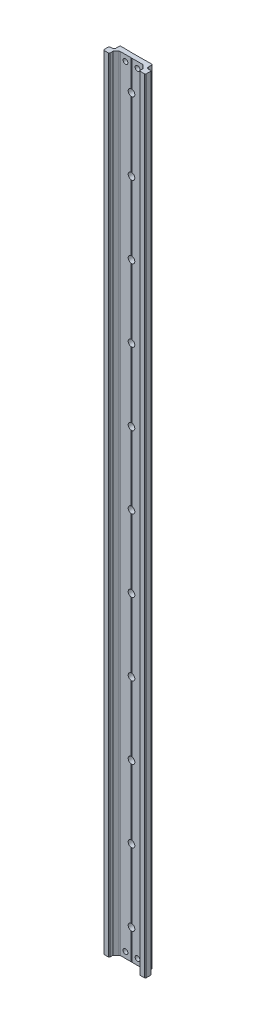
SolidWorks part; units mm, degrees
ref_plane "Plan de face" through (0, 0, 0) normal (0, 0, 1) x (1, 0, 0)
ref_plane "Plan de dessus" through (0, 0, 0) normal (0, 1, 0) x (1, 0, 0)
ref_plane "Plan de droite" through (0, 0, 0) normal (1, 0, 0) x (0, 0, -1)
ref_plane "Plan1" through (0, 325, 0) normal (0, 1, 0) x (1, 0, 0)
sketch "Esquisse1" plane through (0, 325, 0) normal (0, 1, 0) x (1, 0, 0)
  line L0 (-9.7, 1) -> (9.7, 1)
  line L1 (9.7, 1) -> (12.5, -1.8)
  line L2 (12.5, -1.8) -> (12.5, -5)
  line L3 (12.5, -5) -> (17.5, -5)
  line L4 (17.5, -5) -> (17.5, 5)
  line L5 (17.5, 5) -> (-17.5, 5)
  line L6 (-17.5, 5) -> (-17.5, -5)
  line L7 (-17.5, -5) -> (-12.5, -5)
  line L8 (-12.5, -5) -> (-12.5, -1.8)
  line L9 (-12.5, -1.8) -> (-9.7, 1)
extrude "Boss.-Extru.1" add sketch "Esquisse1" against normal blind 650
sketch "Esquisse2" plane through (0, -325, 0) normal (0, -1, 0) x (1, 0, 0)
  line L0 (-14.3, 0) -> (-17.5, 0)
  line L1 (-17.5, 0) -> (-17.5, -5)
  line L2 (-17.5, -5) -> (-13.5, -5)
  line L3 (-13.5, -5) -> (-13.5, -0.8)
  line L4 (-13.5, -0.8) -> (-14.3, 0)
extrude "Enlèv. mat.-Extru.1" cut sketch "Esquisse2" against normal through all
sketch "Esquisse3" plane through (0, -325, 0) normal (0, -1, 0) x (1, 0, 0)
  line L0 (0.25, -1) -> (-0.25, -1)
  line L1 (-0.25, -1) -> (0, -1.1443)
  line L2 (0, -1.1443) -> (0.25, -1)
extrude "Enlèv. mat.-Extru.2" cut sketch "Esquisse3" against normal blind 650
sketch "Esquisse4" plane through (0, -325, 0) normal (0, -1, 0) x (1, 0, 0)
  line L0 (13.5, -0.8) -> (13.5, -5)
  line L1 (13.5, -5) -> (17.5, -5)
  line L2 (17.5, -5) -> (17.5, 0)
  line L3 (17.5, 0) -> (14.3, 0)
  line L4 (14.3, 0) -> (13.5, -0.8)
extrude "Enlèv. mat.-Extru.3" cut sketch "Esquisse4" against normal through all
sketch "Esquisse5" plane through (0, -325, 0) normal (0, -1, 0) x (1, 0, 0)
  line L0 (-7.5, -5) -> (7.5, -5)
  line L1 (7.5, -5) -> (7.4, -4.9)
  line L2 (7.4, -4.9) -> (-7.4, -4.9)
  line L3 (-7.4, -4.9) -> (-7.5, -5)
extrude "Enlèv. mat.-Extru.4" cut sketch "Esquisse5" against normal blind 650
hole_wizard "Diamètre du perçage Ø5.5 (5.5)1" positions "Esquisse7" profile "Esquisse6" hole size "Ø5.5" standard "Ansi Metric"
sketch "Esquisse7" plane through (0, 0, -4.9) normal (0, 0, -1) x (-1, 0, 0)
  point P0 (0, 300)
  point P1 (0, 240)
  point P2 (0, 180)
  point P3 (0, 120)
  point P4 (0, 60)
  point P5 (0, 0)
  point P6 (0, -60)
  point P7 (0, -120)
  point P8 (0, -180)
  point P9 (0, -240)
  point P10 (0, -300)
sketch "Esquisse6" plane through (0, 300, -4.9) normal (1, 0, 0) x (0, 1, 0)
  line L0 (0, 0) -> (0, 9.9)
  line L1 (0, 9.9) -> (2.75, 9.9)
  line L2 (2.75, 9.9) -> (2.75, 0)
  line L5 (2.75, 0) -> (0, 0)
  line L11 (0, -6.35) -> (0, 107.95) construction
  dimension "Diamètre du perçage jusqu'au prochain" = 5.5
  dimension "Profondeur du perçage jusqu'au prochain" = 9.9
chamfer "Chanfrein1" distance 0.5 angle 45 2 edges at (17.5, 0, 5) (-17.5, 0, 5) first distance on face at (17.5, 0, 2.5) first distance on face at (-15, 0, 5)
chamfer "Chanfrein2" distance 0.3 angle 45 2 edges at (-13.5, 0, -5) (13.5, 0, -5)
chamfer "Chanfrein3" distance 0.5 angle 45 3 edges at (12.5, 0, 5) (-17.5, 0, 0) (-12.5, 0, 5) first distance on face at (14.75, 0, 5) first distance on face at (-15.9, 0, 0) first distance on face at (-12.5, 0, 3.4)
chamfer "Chanfrein4" distance 0.5 angle 45 1 edges at (17.5, 0, 0) first distance on face at (15.9, 0, 0)
fillet "Congé1" radius 1.5 2 edges at (9.7, 0, -1) (-9.7, 0, -1) tangent propagation no
fillet "Congé2" radius 2 2 edges at (13.5, 0, -0.8) (-13.5, 0, -0.8) tangent propagation no
sketch "Esquisse8" plane through (0, 0, -1) normal (0, 0, 1) x (1, 0, 0)
  line L0 (-9.0787, -325) -> (-0.25, -325) construction
  line L1 (0.25, -325) -> (9.0787, -325) construction
  line L2 (-9.0787, 325) -> (-0.25, 325) construction
  line L3 (0.25, 325) -> (9.0787, 325) construction
  line L4 (0, 325) -> (0, 302.75) construction
  circle A0 centre (-5, -320) radius 2
  circle A1 centre (5, -320) radius 2
  circle A2 centre (-5, 320) radius 2
  circle A3 centre (5, 320) radius 2
  dimension "D1" = 4
  dimension "D2" = 4
  dimension "D3" = 4
  dimension "D4" = 4
  dimension "D5" = 5
  dimension "D6" = 5
  dimension "D7" = 5
  dimension "D8" = 5
  dimension "D9" = 5
  dimension "D10" = 5
  dimension "D11" = 5
  dimension "D12" = 5
extrude "Enlèv. mat.-Extru.5" cut sketch "Esquisse8" against normal blind 10
